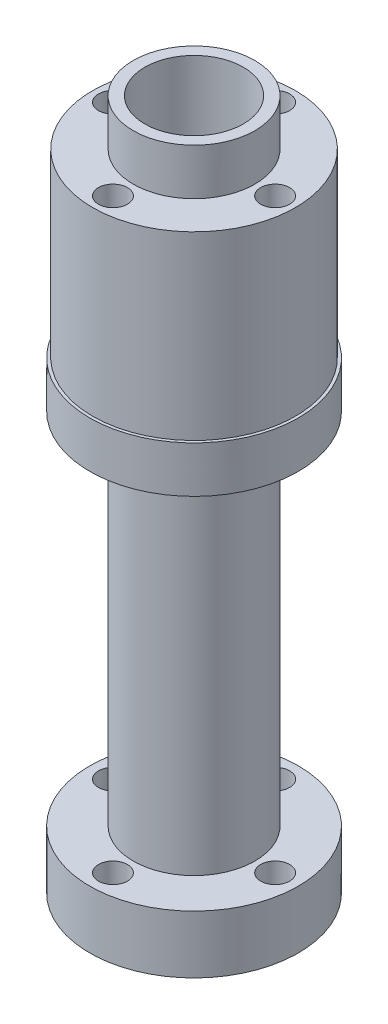
SolidWorks part; units mm, degrees
other "细节项目1"
other "细节项目2"
material "6061-T6 (SS)"
ref_plane "前视基准面" through (0, 0, 0) normal (0, 0, 1) x (1, 0, 0)
ref_plane "上视基准面" through (0, 0, 0) normal (0, 1, 0) x (1, 0, 0)
ref_plane "右视基准面" through (0, 0, 0) normal (1, 0, 0) x (0, 0, -1)
sketch "草图1" plane through (0, 0, 0) normal (0, 0, 1) x (1, 0, 0)
  line L0 (0, 0) -> (0, 22.2724) construction
  line L1 (-9, 36) -> (-5.25, 36)
  line L2 (-4.25, 0) -> (-9, 0)
  line L3 (-4.25, 0) -> (-4.25, 55.6)
  line L4 (-4.25, 55.6) -> (-9, 55.6)
  line L5 (-9, 0) -> (-9, 5)
  line L6 (-5.25, 36) -> (-5.25, 5)
  line L7 (-5.25, 5) -> (-9, 5)
  line L8 (-9, 36) -> (-9, 55.6)
  dimension "D1" = 8.5
  dimension "D2" = 18
  dimension "D3" = 55.6
  dimension "D4" = 36
  dimension "D5" = 5
  dimension "D6" = 1
revolve "旋转1" add sketch "草图1" angle 360 about L0
sketch "草图2" plane through (0, 55.6, 0) normal (0, 1, 0) x (1, 0, 0)
  circle A0 centre (0, 0) radius 7 construction
  circle A1 centre (0, 7) radius 1.25
  circle A2 centre (0, -7) radius 1.25
  circle A3 centre (-7, 0) radius 1.25
  circle A4 centre (7, 0) radius 1.25
  dimension "D1" = 14
  dimension "D2" = 2.5
extrude "切除-拉伸1" cut sketch "草图2" against normal blind 10
cosmetic thread "装饰螺纹线3" parameters "D2"=3
cosmetic thread "装饰螺纹线4" parameters "D2"=3
cosmetic thread "装饰螺纹线5" parameters "D2"=3
cosmetic thread "装饰螺纹线6" parameters "D2"=3
extrude "切除-拉伸2" cut sketch "草图2<2>" along normal blind 6 from surface starting at face at (0, 0, -4.25)
sketch "草图2<2>" plane through (0, 55.6, 0) normal (0, 1, 0) x (1, 0, 0) same geometry as "草图2"
cosmetic thread "装饰螺纹线1" parameters "D2"=3
cosmetic thread "装饰螺纹线2" parameters "D2"=3
sketch "草图3" plane through (0, 55.6, 0) normal (0, 1, 0) x (1, 0, 0)
  circle A0 centre (0, 0) radius 8.75
  dimension "D1" = 17.5
extrude "切除-拉伸3" cut sketch "草图3" against normal offset from surface (15.6 mm away) 4 flip side to cut up to face at (0, 36, -5.25)
sketch "草图4" plane through (0, 55.6, 0) normal (0, 1, 0) x (1, 0, 0)
  circle A0 centre (0, 0) radius 5.25
  circle A1 centre (0, 0) radius 4.25 construction
  circle A2 centre (0, 0) radius 4.25
  dimension "D1" = 10.5
extrude "凸台-拉伸1" add sketch "草图4" along normal blind 4
